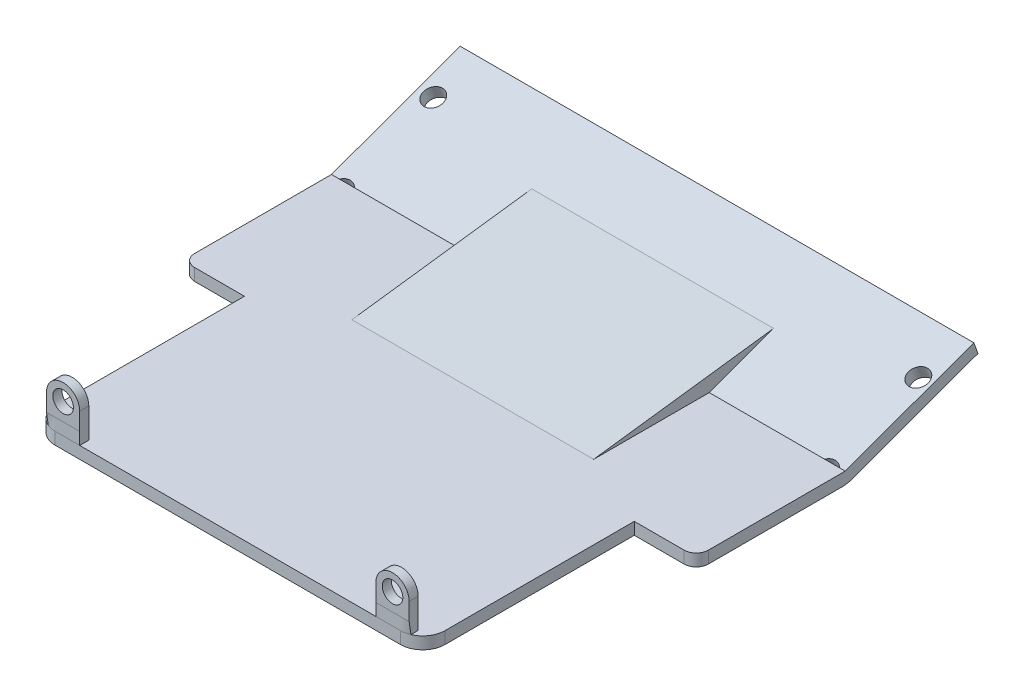
SolidWorks part; units mm, degrees
ref_plane "前视基准面" through (0, 0, 0) normal (0, 0, 1) x (1, 0, 0)
ref_plane "上视基准面" through (0, 0, 0) normal (0, 1, 0) x (1, 0, 0)
ref_plane "右视基准面" through (0, 0, 0) normal (1, 0, 0) x (0, 0, -1)
sketch "草图1" plane through (0, 0, 0) normal (0, 1, 0) x (1, 0, 0)
  line L0 (-15, -259.0169) -> (-15, 12805.6838) construction
  line L1 (15, -261.2731) -> (15, 12803.4276) construction
  line L2 (0, -1000) -> (0, 49000) construction
  line L3 (-1006.7233, 60) -> (48993.2767, 60) construction
  line L4 (-1005.83, 0) -> (48994.17, 0) construction
  line L5 (-1015, 1.7) -> (48985, 1.7) construction
  line L6 (-1015, 58.3) -> (48985, 58.3) construction
  line L7 (-32.25, -984.2827) -> (-32.25, 49015.7173) construction
  line L8 (32.25, -985.1) -> (32.25, 49014.9) construction
  line L9 (-28.55, 62) -> (28.55, 62)
  line L10 (32.25, 58.3) -> (32.25, 1.7)
  line L11 (28.55, -2) -> (-28.55, -2)
  line L12 (-32.25, 1.7) -> (-32.25, 58.3)
  arc A5 (-32.25, 1.7) -> (-28.55, -2) centre (-28.55, 1.7) ccw
  arc A6 (32.25, 1.7) -> (28.55, -2) centre (28.55, 1.7) cw
  arc A7 (28.55, 62) -> (32.25, 58.3) centre (28.55, 58.3) cw
  arc A8 (-28.55, 62) -> (-32.25, 58.3) centre (-28.55, 58.3) ccw
  dimension "D4" = 56.6
  dimension "D8" = 64.5
  dimension "D1" = 30
  dimension "D2" = 15
  dimension "D3" = 60
  dimension "D9" = 32.25
extrude "凸台-拉伸2" add sketch "草图1" against normal blind 2
sketch "草图4" plane through (0, 0, 0) normal (0, 1, 0) x (1, 0, 0)
  line L0 (-25.5, -990.3861) -> (-25.5, 49009.6139) construction
  line L1 (25.5, -991.9534) -> (25.5, 49008.0466) construction
  line L2 (-29, -982.9974) -> (-29, 49017.0026) construction
  line L3 (29, -984.9677) -> (29, 49015.0323) construction
  line L4 (0, -1000) -> (0, 49000) construction
  line L8 (-28.55, -2) -> (28.55, -2) construction
  line L14 (-30, -998.5041) -> (-30, 49001.4959) construction
  line L15 (-24.5, -999.0098) -> (-24.5, 49000.9902) construction
  line L17 (-30, -0.5) -> (-30, -1.704)
  line L18 (-30, -0.5) -> (-24.5, -0.5)
  line L19 (-24.5, -0.5) -> (-24.5, -2)
  line L20 (-28.55, -2) -> (-24.5, -2)
  arc A2 (-28.55, -2) -> (-30, -1.704) centre (-28.55, 1.7) cw
  dimension "D6" = 1
  dimension "D1" = 51
  dimension "D2" = 58
  dimension "D3" = 29
  dimension "D4" = 25.5
  dimension "D7" = 1
ref_plane "基准面4" through (0, 2, 0) normal (0, 1, 0) x (1, 0, 0)
sketch "草图5" plane through (0, 2, 0) normal (0, 1, 0) x (1, 0, 0)
  line L6 (-30, -200998.5041) -> (-30, 249001.4959) construction
  line L7 (-30, -2) -> (-30, -0.5)
  line L8 (-30, -0.5) -> (-24.5, -0.5)
  line L9 (-24.5, -0.5) -> (-24.5, -2)
  line L11 (-24.5, -2) -> (-28.55, -2)
  line L12 (-28.55, -2) -> (-30, -2)
loft "放样4" add profiles "草图4", "草图5" connector at (-24.5, 0, 2) connector at (-24.5, 2, 2)
sketch "草图6" plane through (0, 0, 0) normal (0, 0, 1) x (1, 0, 0)
  line L0 (-1028.1213, 3.2) -> (48971.8787, 3.2) construction
  line L1 (-24.5, 0) -> (28.55, 0) construction
  line L2 (-1026.7035, 6.6) -> (48973.2965, 6.6) construction
  line L3 (-24.5, 4.9) -> (-24.5, 2)
  line L4 (-24.5, 2) -> (-24.5, 0) construction
  line L5 (-30, 2) -> (-30, 4.9)
  line L6 (35.475, 2) -> (-35.475, 2) construction
  line L7 (-30, 0) -> (-30, 2) construction
  line L8 (-30, 2) -> (-24.5, 2)
  circle A0 centre (-27.25, 4.9) radius 1.7
  arc A1 (-24.5, 4.9) -> (-30, 4.9) centre (-27.25, 4.9) ccw
  dimension "D3" = 2.75
  dimension "D1" = 3.2
  dimension "D2" = 3.4
extrude "凸台-拉伸3" add sketch "草图6" along normal blind 1.5 from offset 0.5
mirror "镜向1" about plane through (0, 0, 0) normal (1, 0, 0) of "放样4", "凸台-拉伸3"
sketch "草图7" plane through (0, 0, 0) normal (0, 1, 0) x (1, 0, 0)
  line L0 (-42.5, 58) -> (42.5, 58)
  line L1 (42.5, 58) -> (42.5, 33)
  line L2 (42.5, 33) -> (-42.5, 33)
  line L3 (-42.5, 33) -> (-42.5, 58)
  line L4 (28.55, 62) -> (-28.55, 62) construction
  line L5 (0, 62) -> (0, 58) construction
  dimension "D1" = 85
  dimension "D2" = 42.5
  dimension "D3" = 4
  dimension "D4" = 25
extrude "凸台-拉伸4" add sketch "草图7" against normal blind 2
fillet "圆角2" radius 10 1 edges at (-32.25, -1, -58)
fillet "圆角4" radius 10 1 edges at (32.25, -1, -58)
sketch "草图9" plane through (0, 0, 0) normal (0, 1, 0) x (1, 0, 0)
  line L0 (-38.2247, 58) -> (-42.5, 58) construction
  line L1 (-51.2589, 67.4647) -> (50.0267, 67.4647)
  line L2 (-51.2589, 67.4647) -> (-51.2589, 58)
  line L3 (-51.2589, 58) -> (50.0267, 58)
  line L4 (50.0267, 67.4647) -> (50.0267, 58)
extrude "切除-拉伸2" cut sketch "草图9" against normal blind 2
fillet "圆角8" radius 2 1 edges at (-42.5, -1, -33)
fillet "圆角9" radius 2 1 edges at (42.5, -1, -33)
sketch "草图10" plane through (42.5, 0, 0) normal (1, 0, 0) x (0, 0, -1)
  line L0 (58, -2) -> (79.6129, 5.8665)
  line L1 (35, -2) -> (58, -2) construction
  line L3 (78.9289, 7.7458) -> (57.316, -0.1206)
  line L5 (78.9289, 7.7458) -> (79.6129, 5.8665)
  line L6 (58, -2) -> (57.316, -0.1206)
  line L7 (58, -2) -> (40.1911, -8.4819) construction
  dimension "D1" = 160
  dimension "D2" = 2
  dimension "D3" = 90
  dimension "D4" = 2
  dimension "D5" = 90
  dimension "D6" = 23
  dimension "D7" = 20
extrude "凸台-拉伸5" add sketch "草图10" against normal up to surface (85 mm away) up to face at (-42.5, -1, -46.5)
fillet "圆角10" radius 5 1 edges at (0, -2, -58)
sketch "草图13" plane through (0, -18.5275, -6.7435) normal (0, 0.9397, 0.342) x (1, 0, 0)
  line L0 (-39.936, 69.3659) -> (40.314, 69.3659) construction
  line L1 (0, 69.3659) -> (0, 0) construction
  line L2 (-39.936, 69.3659) -> (-39.936, 53.1159) construction
  line L3 (-39.936, 53.1159) -> (40.314, 53.1159) construction
  line L4 (40.314, 53.1159) -> (40.314, 69.3659) construction
  circle A0 centre (-39.936, 69.3659) radius 1.625
  circle A1 centre (40.314, 69.3659) radius 1.625
  circle A2 centre (40.314, 53.1159) radius 1.625
  circle A3 centre (-39.936, 53.1159) radius 1.625
  dimension "D3" = 3.25
  dimension "D4" = 3.25
  dimension "D5" = 3.25
  dimension "D6" = 3.25
  dimension "D1" = 80.25
  dimension "D2" = 16.25
extrude "切除-拉伸3" cut sketch "草图13" against normal blind 10
ref_plane "基准面5" through (0, 0, 0) normal (-1, 0, 0) x (0, 0, 1)
sketch "草图14" plane through (0, 0, 0) normal (-1, 0, 0) x (0, 0, 1)
  line L0 (-68.2881, 3.8729) -> (-38.5265, 0)
  line L1 (-78.9289, 7.7458) -> (-57.6473, 0) construction
  line L2 (-57.6473, 0) -> (-35, 0) construction
  line L3 (-68.2881, 3.8729) -> (-57.6473, 0)
  line L4 (-57.6473, 0) -> (-38.5265, 0)
  point P6 (-38.5265, 0)
extrude "凸台-拉伸6" add sketch "草图14" along normal mid plane 40
